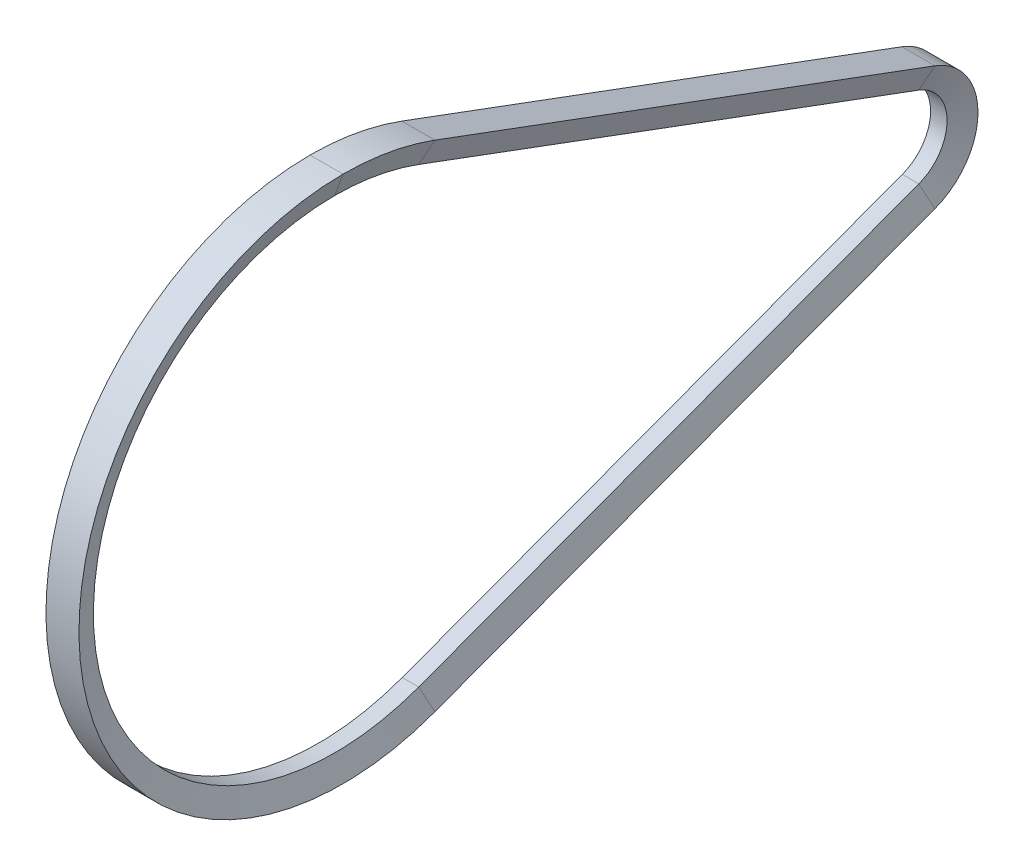
SolidWorks part; units mm, degrees
material "NEOPRENO"
ref_plane "Front" through (0, 0, 0) normal (0, 0, 1) x (1, 0, 0)
ref_plane "Top" through (0, 0, 0) normal (0, 1, 0) x (1, 0, 0)
ref_plane "Right" through (0, 0, 0) normal (1, 0, 0) x (0, 0, -1)
sketch "Croquis1" plane through (0, 0, 0) normal (1, 0, 0) x (0, 0, -1)
  line L0 (0, 0) -> (218.948, 0) construction
  line L1 (227.7879, 23.8121) -> (35.3596, 95.2484)
  line L2 (227.7879, -23.8121) -> (35.3596, -95.2484)
  arc A0 (35.3596, 95.2484) -> (35.3596, -95.2484) centre (0, 0) ccw
  arc A1 (227.7879, -23.8121) -> (227.7879, 23.8121) centre (218.948, 0) ccw
  dimension "D1" = 203.2
  dimension "D2" = 50.8
  dimension "D3" = 218.948
sketch "Croquis2" plane through (0, 0, 0) normal (0, 0, 1) x (1, 0, 0)
  line L0 (-6.35, 101.6) -> (6.35, 101.6)
  line L1 (0, 23.8121) -> (0, 95.2484) construction
  line L2 (0, -101.6) -> (0, 101.6) construction
  line L3 (6.35, 101.6) -> (3.1721, 92.8687)
  line L4 (3.1721, 92.8687) -> (-3.1721, 92.8687)
  line L5 (0, 101.6) -> (0, 92.8688) construction
  line L6 (-6.35, 101.6) -> (-3.1721, 92.8687)
  dimension "D1" = 6.35
  dimension "D2" = 8.7312
  dimension "D3" = 20
sweep "Barrer1" add profiles "Croquis2" path "Croquis1"
